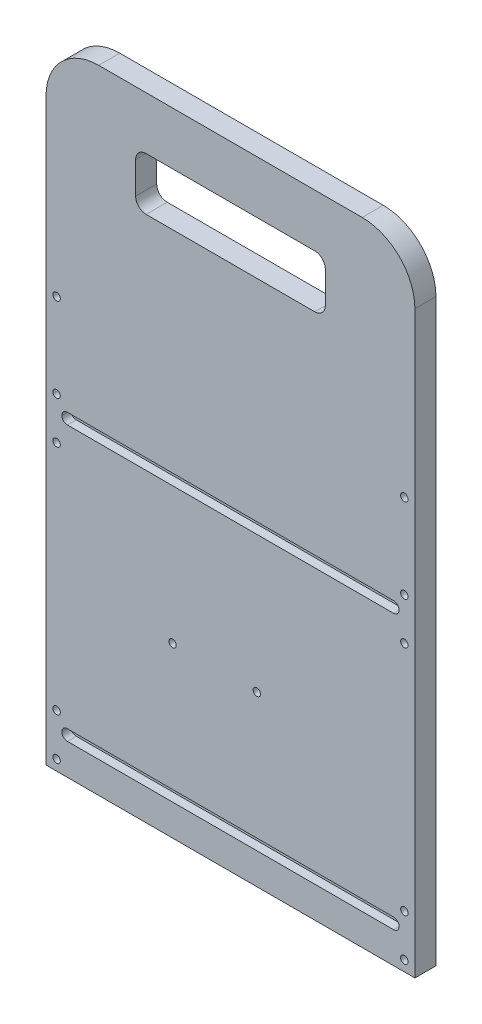
SolidWorks part; units mm, degrees
material "Delrin 2700 NC010, Low Viscosity Acetal Copolymer (SS)"
ref_plane "Front Plane" through (0, 0, 0) normal (0, 0, 1) x (1, 0, 0)
ref_plane "Top Plane" through (0, 0, 0) normal (0, 1, 0) x (1, 0, 0)
ref_plane "Right Plane" through (0, 0, 0) normal (1, 0, 0) x (0, 0, -1)
sketch "Sketch1" plane through (0, 0, 0) normal (0, 0, 1) x (1, 0, 0)
  line L1 (-111.125, -190.5) -> (111.125, -190.5)
  line L2 (-111.125, -190.5) -> (-111.125, 190.5)
  line L3 (-111.125, 190.5) -> (111.125, 190.5)
  line L4 (111.125, -190.5) -> (111.125, 190.5)
  line L5 (-111.125, -190.5) -> (111.125, 190.5) construction
  line L6 (-111.125, 190.5) -> (111.125, -190.5) construction
  point P0 (0, 0)
  dimension "D1" = 222.25
  dimension "D2" = 381
extrude "Boss-Extrude1" add sketch "Sketch1" along normal blind 12.7 contours L3 L4 L1 L2
fillet "Fillet1" radius 31.75 2 edges at (-111.125, 190.5, 6.35) (111.125, 190.5, 6.35)
sketch "Sketch2" plane through (0, 0, 12.7) normal (0, 0, 1) x (1, 0, 0)
  line L0 (-79.375, 190.5) -> (79.375, 190.5) construction
  line L1 (-57.15, 158.75) -> (57.15, 158.75)
  line L2 (-57.15, 158.75) -> (-57.15, 127)
  line L3 (-57.15, 127) -> (57.15, 127)
  line L4 (57.15, 158.75) -> (57.15, 127)
  point P4 (0, 127)
  dimension "D1" = 114.3
  dimension "D2" = 31.75
  dimension "D3" = 31.75
extrude "Cut-Extrude1" cut sketch "Sketch2" against normal up to surface (12.7 mm away) up to face at (0, 55.1085, 0)
fillet "Fillet2" radius 6.35 4 edges at (57.15, 127, 6.35) (57.15, 158.75, 6.35) (-57.15, 158.75, 6.35) (-57.15, 127, 6.35)
sketch "Sketch3" plane through (0, 0, 12.7) normal (0, 0, 1) x (1, 0, 0)
  line L0 (-111.125, -190.5) -> (111.125, -190.5) construction
  line L1 (-101.6, -171.704) -> (101.6, -171.704)
  line L2 (-101.6, -171.704) -> (-101.6, -165.1)
  line L3 (-101.6, -165.1) -> (101.6, -165.1)
  line L4 (101.6, -171.704) -> (101.6, -165.1)
  line L6 (-101.6, -6.604) -> (101.6, -6.604)
  line L7 (-101.6, -6.604) -> (-101.6, 0)
  line L8 (-101.6, 0) -> (101.6, 0)
  line L9 (101.6, -6.604) -> (101.6, 0)
  point P4 (0, -165.1)
  point P12 (0, -6.604)
  dimension "D1" = 18.796
  dimension "D2" = 6.604
  dimension "D3" = 203.2
  dimension "D4" = 203.2
  dimension "D5" = 6.604
  dimension "D6" = 183.896
extrude "Cut-Extrude2" cut sketch "Sketch3" against normal blind 5.334
fillet "Fillet3" radius 3.302 8 edges at (101.6, -165.1, 10.033) (101.6, -171.704, 10.033) (-101.6, -171.704, 10.033) (-101.6, -165.1, 10.033) (101.6, -6.604, 10.033) (101.6, 0, 10.033) (-101.6, 0, 10.033) (-101.6, -6.604, 10.033)
hole_wizard "CSK for #8 Flat Head Machine Screw (100)1" positions "Sketch6" profile "Sketch8" countersink size "#8" standard "ANSI Inch" end condition through all
sketch "Sketch6" plane through (0, 0, 0) normal (0, 0, -1) x (-1, 0, 0)
  line L0 (111.125, -190.5) -> (-111.125, -190.5) construction
  line L1 (-111.125, -190.5) -> (-111.125, 158.75) construction
  line L2 (111.125, -190.5) -> (111.125, 158.75) construction
  line L3 (111.125, -190.5) -> (111.125, 158.75) construction
  point P0 (-104.775, -184.15)
  point P2 (-104.775, -158.75)
  point P4 (104.775, -158.75)
  point P6 (104.775, -184.15)
  point P20 (-104.775, -19.05)
  point P22 (-104.775, 6.35)
  point P24 (104.775, 6.35)
  point P26 (104.775, -19.05)
  point P35 (-104.775, 57.15)
  point P37 (104.775, 57.15)
  point P43 (-15.875, -88.9)
  point P45 (34.925, -88.9)
  dimension "D1" = 6.35
  dimension "D2" = 6.35
  dimension "D3" = 6.35
  dimension "D4" = 25.4
  dimension "D5" = 171.45
  dimension "D6" = 25.4
  dimension "D7" = 50.8
  dimension "D8" = 50.8
  dimension "D10" = 101.6
  dimension "D9" = 76.2
sketch "Sketch8" plane through (104.775, -184.15, 0) normal (1, 0, 0) x (0, 1, 0)
  line L0 (0, 0) -> (0, 12.7)
  line L1 (0, 12.7) -> (2.2479, 12.7)
  line L2 (2.2479, 12.7) -> (2.2479, 1.6518)
  line L3 (2.2479, 1.6518) -> (4.2164, 0)
  line L5 (4.2164, 0) -> (0, 0)
  line L6 (-2.2479, 1.6518) -> (-4.2164, 0) construction
  line L11 (0, -6.35) -> (0, 107.95) construction
  dimension "Thru Hole Dia." = 4.4958
  dimension "Thru Hole Depth" = 12.7
  dimension "Near C'Sink Dia." = 8.4328
  dimension "Near C'Sink Angle" = 100
equation "\"D4@Sketch3\"=\"D3@Sketch3\""
equation "\"D5@Sketch3\"=\"D2@Sketch3\""
equation "\"D3@Sketch6\"=\"D2@Sketch6\""
equation "\"D6@Sketch6\"=\"D4@Sketch6\""
